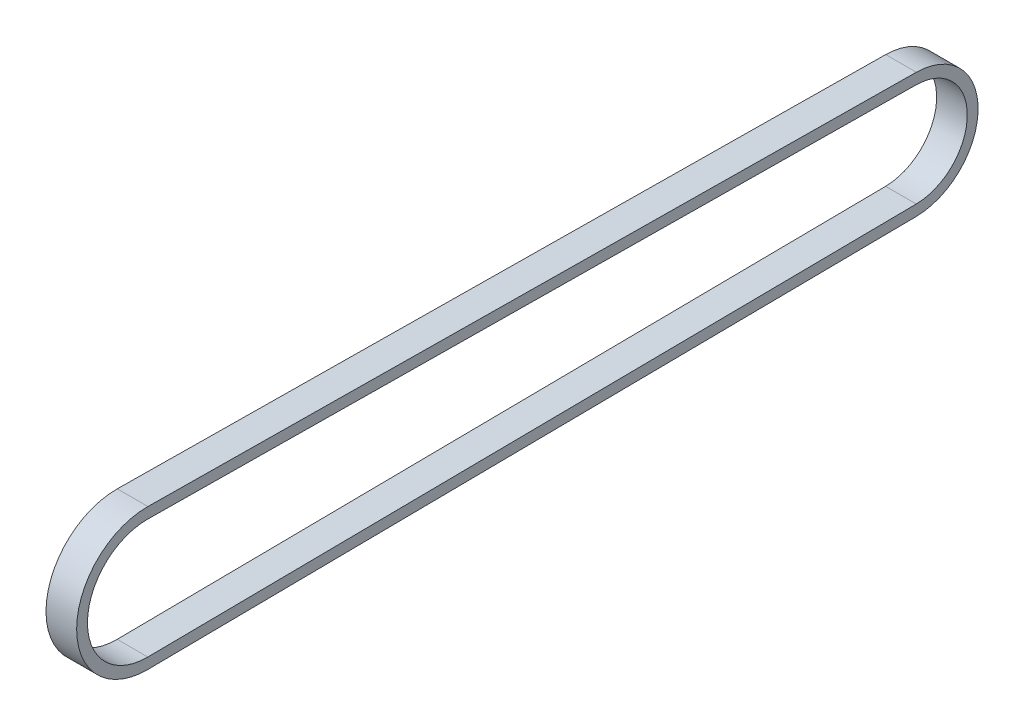
SolidWorks part; units mm, degrees
ref_plane "Front Plane" through (0, 0, 0) normal (0, 0, 1) x (1, 0, 0)
ref_plane "Top Plane" through (0, 0, 0) normal (0, 1, 0) x (1, 0, 0)
ref_plane "Right Plane" through (0, 0, 0) normal (1, 0, 0) x (0, 0, -1)
other "Bounding Box"
ref_plane "Default Plane" through (-8.9266, -12.7485, 0) normal (-0.1736, 0.9848, 0) x (0.9848, 0.1736, 0)
sketch "Sketch1" plane through (0, 0, 0) normal (1, 0, 0) x (0, 0, -1)
  line L0 (0, 0) -> (225.7374, 0) construction
  line L1 (0.1854, 17.5479) -> (225.8976, 15.163)
  line L2 (0.1854, -17.5479) -> (225.8976, -15.163)
  line L3 (0.219, 20.7227) -> (225.9312, 18.3378)
  line L4 (0.219, -20.7227) -> (225.9312, -18.3378)
  line L5 (-17.5489, 0) -> (-20.7239, 0) construction
  line L6 (240.9012, 0) -> (244.0762, 0) construction
  arc A0 (0.1854, 17.5479) -> (0.1854, -17.5479) centre (0, 0) ccw
  arc A1 (225.8976, -15.163) -> (225.8976, 15.163) centre (225.7374, 0) ccw
  arc A2 (0.219, 20.7227) -> (0.219, -20.7227) centre (0, 0) ccw
  arc A3 (225.9312, -18.3378) -> (225.9312, 18.3378) centre (225.7374, 0) ccw
  dimension "D2" = 3.175
  dimension "D3" = 15.1638
  dimension "D4" = 35.0977
  dimension "D1" = 225.7374
extrude "Boss-Extrude1" add sketch "Sketch1" along normal mid plane 9
